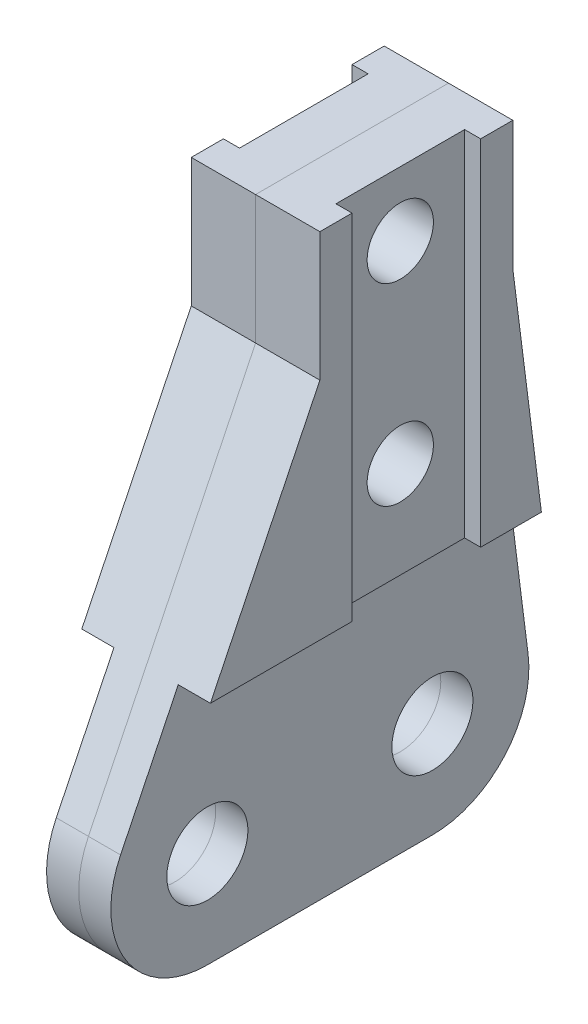
SolidWorks part; units mm, degrees
ref_plane "Front Plane" through (0, 0, 0) normal (0, 0, 1) x (1, 0, 0)
ref_plane "Top Plane" through (0, 0, 0) normal (0, 1, 0) x (1, 0, 0)
ref_plane "Right Plane" through (0, 0, 0) normal (1, 0, 0) x (0, 0, -1)
sketch "Sketch1" plane through (0, 0, 0) normal (1, 0, 0) x (0, 0, -1)
  line L0 (-22.225, -41.275) -> (22.225, -41.275) construction
  line L1 (0, -41.275) -> (0, 60.325) construction
  line L2 (-6.35, 34.925) -> (31.75, 34.925) construction
  line L3 (-22.225, -60.325) -> (22.225, -60.325)
  line L4 (0, 60.325) -> (31.75, 60.325)
  line L5 (-6.35, 60.325) -> (-6.35, 34.925)
  line L6 (0, 60.325) -> (-6.35, 60.325)
  line L7 (31.75, 60.325) -> (31.75, 34.925)
  line L8 (-6.35, 34.925) -> (-39.3565, -32.9434)
  line L9 (31.75, 34.925) -> (41.1232, -38.8748)
  circle A0 centre (-22.225, -41.275) radius 8.001
  circle A1 centre (22.225, -41.275) radius 8.001
  circle A2 centre (-22.225, -41.275) radius 19.05
  circle A3 centre (22.225, -41.275) radius 19.05
extrude "Boss-Extrude1" add sketch "Sketch1" along normal blind 12.7 contours A3 L9 L7 L4 L6 L5 L8 A2 L3 | A3 A1 | A2 A0 region at (0, 6.6516, -7.5075) region at (0, -51.0933, 37.9178) region at (0, -29.038, -8.3355)
sketch "Sketch2" plane through (12.7, 0, 0) normal (1, 0, 0) x (0, 0, -1)
  line L0 (-22.225, -60.325) -> (22.225, -60.325) construction
  line L1 (-22.225, -60.325) -> (22.225, -60.325)
  line L2 (-22.225, -41.275) -> (22.225, -41.275) construction
  line L3 (-22.225, -22.225) -> (22.225, -22.225)
  line L4 (-22.225, -60.325) -> (22.225, -60.325)
  line L5 (0, 60.325) -> (0, -22.225)
  line L6 (-6.35, 60.325) -> (31.75, 60.325) construction
  line L7 (25.4, -22.4914) -> (25.4, 60.325)
  line L8 (31.75, 60.325) -> (31.75, 34.925) construction
  line L11 (-63.9631, -73.025) -> (63.9631, -73.025)
  line L12 (-63.9631, -73.025) -> (-63.9631, -9.525)
  line L13 (-63.9631, -9.525) -> (63.9631, -9.525)
  line L14 (63.9631, -73.025) -> (63.9631, -9.525)
  line L15 (-63.9631, -73.025) -> (63.9631, -9.525) construction
  line L16 (-63.9631, -9.525) -> (63.9631, -73.025) construction
  circle A0 centre (22.225, -41.275) radius 8.001 construction
  circle A1 centre (-22.225, -41.275) radius 8.001 construction
  circle A2 centre (22.225, -41.275) radius 8.001
  circle A3 centre (-22.225, -41.275) radius 8.001
  arc A4 (-22.225, -22.225) -> (-22.225, -60.325) centre (-22.225, -41.275) ccw
  arc A5 (22.225, -60.325) -> (22.225, -22.225) centre (22.225, -41.275) ccw
  point P8 (0, -41.275)
  point P23 (0, -41.275)
  line M12 (31.75, 60.325) -> (-6.35, 60.325)
  dimension "D1" = 6.35
  dimension "D2" = 63.5
extrude "Cut-Extrude1" cut sketch "Sketch2" against normal blind 6.35 contours L13 L14 L11 L12
extrude "Cut-Extrude2" cut sketch "Sketch2<3>" against normal blind 3.175 contours L3 L13 L7 L5 M12 region at (12.7, 25.4, -12.7)
sketch "Sketch2<3>" plane through (12.7, 0, 0) normal (1, 0, 0) x (0, 0, -1) same geometry as "Sketch2"
mirror "Mirror1" about plane through (0, 0, 0) normal (1, 0, 0) of bodies 103
sketch "Sketch3" plane through (0, 0, 0) normal (-1, 0, 0) x (0, 0, 1)
  line L0 (-12.7, 60.325) -> (-12.7, -60.325) construction
  line L1 (6.35, 60.325) -> (-31.75, 60.325) construction
  line L2 (22.225, -60.325) -> (-22.225, -60.325) construction
  circle A0 centre (-12.7, 47.625) radius 6.5484
  circle A1 centre (-12.7, 9.525) radius 6.5484
  dimension "D3" = 13.0969
  dimension "D1" = 50.8
  dimension "D2" = 12.7
extrude "Cut-Extrude3" cut sketch "Sketch3" against normal through all
